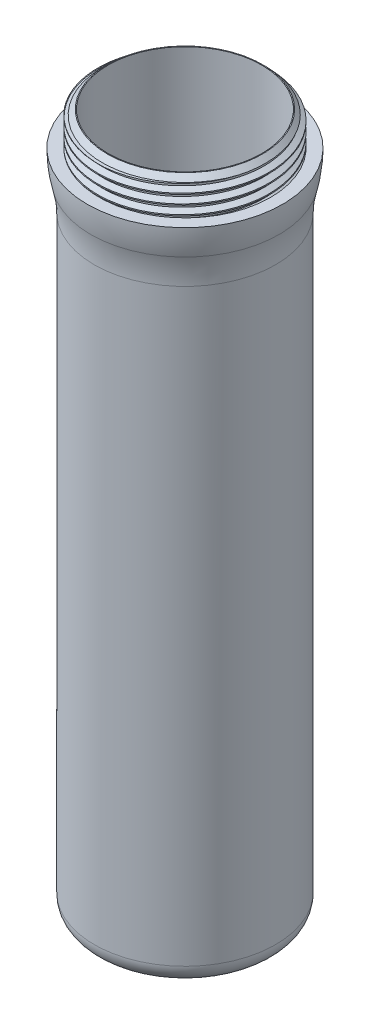
SolidWorks part; units mm, degrees
ref_plane "Front Plane" through (0, 0, 0) normal (0, 0, 1) x (1, 0, 0)
ref_plane "Top Plane" through (0, 0, 0) normal (0, 1, 0) x (1, 0, 0)
ref_plane "Right Plane" through (0, 0, 0) normal (1, 0, 0) x (0, 0, -1)
sketch "Sketch1" plane through (0, 0, 0) normal (0, 1, 0) x (1, 0, 0)
  circle A0 centre (0, 0) radius 17.4625
  circle A1 centre (0, 0) radius 20.6375
  dimension "D1" = 34.925
  dimension "D2" = 3.175
extrude "Boss-Extrude1" add sketch "Sketch1" along normal blind 155.575
sketch "Sketch2" plane through (0, 0, 0) normal (0, -1, 0) x (-1, 0, 0)
  circle A0 centre (0, 0) radius 20.6375
  circle A1 centre (0, 0) radius 20.6375 construction
extrude "Boss-Extrude2" add sketch "Sketch2" along normal blind 3.175
sketch "Sketch13" plane through (0, 155.575, 0) normal (0, 1, 0) x (1, 0, 0)
  line L0 (-19.4945, 0) -> (-17.4625, 0) construction
  circle A0 centre (0, 0) radius 20.6375
  circle A1 centre (0, 0) radius 19.4945
  circle A2 centre (0, 0) radius 17.4625 construction
  circle A3 centre (0, 0) radius 20.6375 construction
  dimension "D1" = 2.032
extrude "Cut-Extrude1" cut sketch "Sketch13" against normal blind 7.62
thread "Thread1" pitch 2.1167 method cut profile "Thread Profile1" start angle 0, offset 2.54, length 0, pitch 2.1167, diameter 38.989
ref_plane "Plane1" through (-19.4945, 158.115, 0) normal (0, 0, 1) x (-1, 0, 0)
sketch "Thread Profile1" plane through (-19.4945, 158.115, 0) normal (0, 0, 1) x (-1, 0, 0)
  line L0 (0, 0) -> (0, 2.1167) construction
  line L11 (0, 0) -> (0, 1.8521)
  line L12 (0, 1.8521) -> (-1.1457, 1.1906)
  line L13 (-1.1457, 1.1906) -> (-1.1457, 0.6615)
  line L15 (-1.1457, 0.6615) -> (0, 0)
  line L17 (-1.1457, 0.926) -> (0, 0.926) construction
  point P2 (0, 0)
  dimension "Pitch" = 2.1167
  dimension "Profile_Angle" = 60
  dimension "Profile_Land" = 0.5292
  dimension "Profile_Height" = 1.1457
sketch "Sketch16" plane through (0, 0, 0) normal (0, 0, 1) x (1, 0, 0)
  line L0 (0, 0) -> (0, 156.9021) construction
  line L1 (-16.51, 156.718) -> (-18.796, 154.432)
  line L2 (-18.796, 154.432) -> (-21.615, 154.432)
  line L3 (-21.615, 154.432) -> (-21.615, 156.718)
  line L4 (-21.615, 156.718) -> (-16.51, 156.718)
  line L6 (20.6375, 147.955) -> (-20.6375, 147.955) construction
  dimension "D1" = 45
  dimension "D2" = 16.51
  dimension "D3" = 2.286
  dimension "D4" = 6.477
revolve "Cut-Revolve1" cut sketch "Sketch16" angle 360 about L0
sketch "Sketch18" plane through (0, 0, 0) normal (0, 0, 1) x (1, 0, 0)
  line L0 (-20.6375, 147.955) -> (-22.225, 147.955)
  line L1 (-20.6375, 147.955) -> (20.6375, 147.955) construction
  line L2 (-22.225, 147.955) -> (-22.225, 138.1492) construction
  line L3 (-20.6375, 147.955) -> (-20.6375, -3.175) construction
  line L4 (-20.6375, 147.955) -> (-20.6375, 135.255)
  line L5 (-22.225, 147.955) -> (-20.6375, 147.955)
  line L6 (0, 147.955) -> (0, 127.601)
  arc A0 (-22.225, 147.955) -> (-21.4312, 141.605) centre (3.5719, 147.955) ccw
  arc A1 (-21.4312, 141.605) -> (-20.6375, 135.255) centre (-46.4344, 135.255) cw
  point P3 (0, 147.955)
  point P17 (-21.4312, 147.955)
  dimension "D1" = 22.225
  dimension "D2" = 12.7
revolve "Revolve1" add sketch "Sketch18" angle 360 about L6 region at (-21.247, 144.2558, 0)
fillet "Fillet1" radius 1.27 1 edges at (0, 0, 17.4625)
fillet "Fillet2" radius 4.445 1 edges at (0, -3.175, -20.6375)
